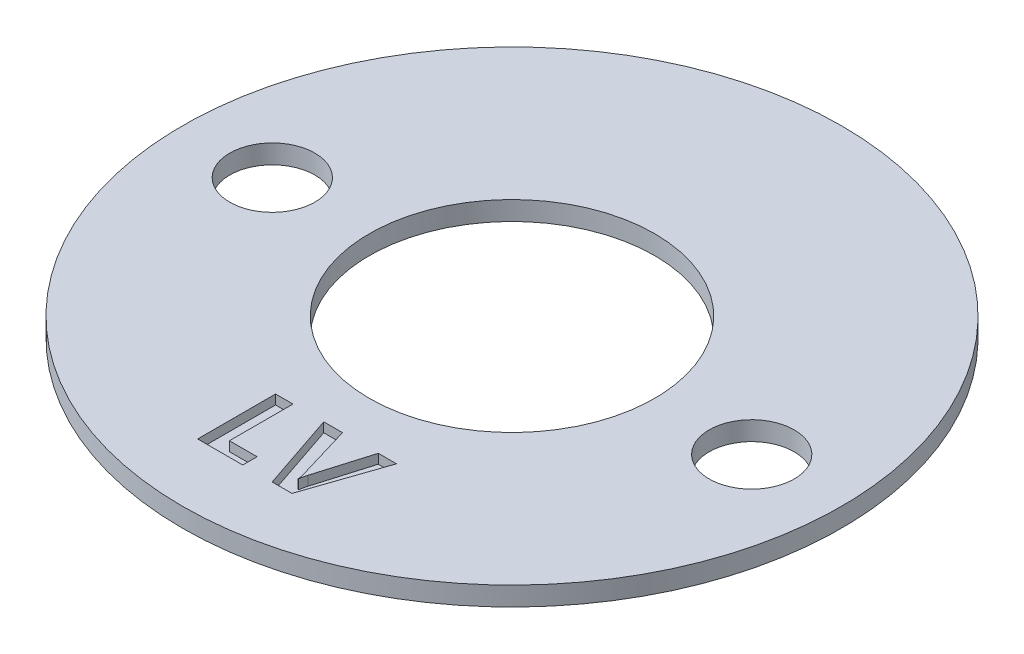
SolidWorks part; units mm, degrees
material "ABS"
ref_plane "Front Plane" through (0, 0, 0) normal (0, 0, 1) x (1, 0, 0)
ref_plane "Top Plane" through (0, 0, 0) normal (0, 1, 0) x (1, 0, 0)
ref_plane "Right Plane" through (0, 0, 0) normal (1, 0, 0) x (0, 0, -1)
sketch "Sketch1" plane through (0, 0, 0) normal (0, 1, 0) x (1, 0, 0)
  circle A0 centre (0, 0) radius 27.5
  dimension "D1" = 55
extrude "Boss-Extrude1" add sketch "Sketch1" along normal blind 1.5875
sketch "Sketch4" plane through (0, 0, 0) normal (0, -1, 0) x (1, 0, 0)
  line L0 (-20.0025, 0) -> (20.0025, 0) construction
  circle A4 centre (-20.0025, 0) radius 3.55
  circle A5 centre (0, 0) radius 11.9062
  circle A6 centre (20.0025, 0) radius 3.55
  dimension "D1" = 40.005
  dimension "D2" = 23.8125
  dimension "D3" = 7.1
extrude "Cut-Extrude2" cut sketch "Sketch4" against normal through all
sketch "Sketch2" plane through (0, 1.5875, 0) normal (0, 1, 0) x (1, 0, 0)
  line L0 (-5, -22) -> (5, -22) construction
  line L1 (0, 0) -> (0, -22) construction
  text T0 "LV" font "Nirmala UI" height 6.5
  dimension "D1" = 10
  dimension "D2" = 22
extrude "Cut-Extrude1" cut sketch "Sketch2" against normal offset from surface (0.7938 mm away) 0.7937 up to face at (-20.0025, 0, -3.55)
